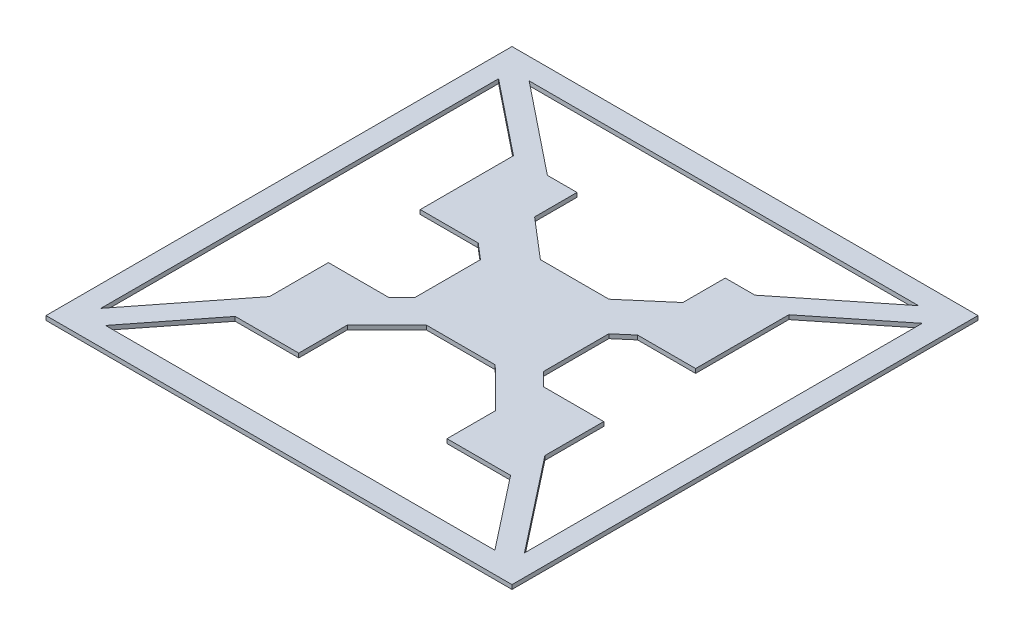
SolidWorks part; units mm, degrees
ref_plane "Спереди" through (0, 0, 0) normal (0, 0, 1) x (1, 0, 0)
ref_plane "Сверху" through (0, 0, 0) normal (0, 1, 0) x (1, 0, 0)
ref_plane "Справа" through (0, 0, 0) normal (1, 0, 0) x (0, 0, -1)
sketch "Эскиз1" plane through (0, 0, 0) normal (0, 1, 0) x (1, 0, 0)
  line L0 (0, 96.4569) -> (0, -119.3284) construction
  line L1 (-128.9937, 0) -> (115.7561, 0) construction
  line L2 (-48.9866, 65.6813) -> (-35, 65.6813)
  line L3 (-65, -21.6813) -> (-36.6417, -21.6813)
  line L4 (-65, -49.475) -> (-65, -21.6813)
  line L5 (-35, -65.6813) -> (-65, -65.6813)
  line L6 (35, -42.7008) -> (35, -65.6813)
  line L7 (36.6417, -21.6813) -> (65, -21.6813)
  line L8 (65, -49.475) -> (65, -21.6813)
  line L9 (-35, -65.6813) -> (-35, -42.7008)
  line L10 (-65, 21.6813) -> (-37.6274, 21.6813)
  line L11 (-16.1862, -24.1069) -> (16.1862, -24.1069)
  line L12 (-35, 45.6702) -> (-35, 65.6813)
  line L13 (-65, 65.6813) -> (-65, 21.6813)
  line L14 (100, 93.6652) -> (100, -94.1115)
  line L15 (35, 65.6813) -> (35, 45.6702)
  line L16 (37.6274, 21.6813) -> (65, 21.6813)
  line L17 (-91.9096, 100) -> (91.9096, 100)
  line L18 (-30.2984, 15.4121) -> (-30.2984, -15.4121)
  line L19 (-16.1862, 29.577) -> (16.1862, 29.577)
  line L20 (30.2984, -15.4121) -> (30.2984, 15.4121)
  line L21 (35, 59.4235) -> (65, 59.4235) construction
  line L22 (48.9866, 65.6813) -> (91.9096, 100)
  line L23 (-110, 110) -> (110, 110)
  line L24 (-110, 110) -> (-110, -110)
  line L25 (-110, -110) -> (110, -110)
  line L26 (110, 110) -> (110, -110)
  line L27 (-100, 93.6652) -> (-100, -94.1115)
  line L28 (35, -65.6813) -> (65, -65.6813)
  line L29 (-91.9096, -100) -> (91.9096, -100)
  line L30 (-65, 59.4235) -> (-35, 59.4235) construction
  line L31 (65, 65.6813) -> (100, 93.6652)
  line L32 (16.1862, 29.577) -> (35, 45.6702)
  line L33 (30.2984, 15.4121) -> (37.6274, 21.6813)
  line L34 (-91.9096, 100) -> (-48.9866, 65.6813)
  line L35 (-100, 93.6652) -> (-65, 65.6813)
  line L36 (-35, 45.6702) -> (-16.1862, 29.577)
  line L37 (-30.2984, 15.4121) -> (-37.6274, 21.6813)
  line L38 (30.2984, -15.4121) -> (36.6417, -21.6813)
  line L39 (16.1862, -24.1069) -> (35, -42.7008)
  line L40 (65, -49.475) -> (100, -94.1115)
  line L41 (65, -65.6813) -> (91.9096, -100)
  line L42 (-36.6417, -21.6813) -> (-30.2984, -15.4121)
  line L43 (-16.1862, -24.1069) -> (-35, -42.7008)
  line L44 (-65, -49.475) -> (-100, -94.1115)
  line L45 (-65, -65.6813) -> (-91.9096, -100)
  line L46 (48.9866, 65.6813) -> (35, 65.6813)
  line L47 (65, 65.6813) -> (65, 21.6813)
  line L48 (-65, -49.4291) -> (-35, -49.4291) construction
  line L49 (35, -49.4291) -> (65, -49.4291) construction
  point P8 (65, -35.5781)
  point P12 (-50, 59.4235)
  point P17 (50, 59.4235)
  point P20 (-50, -49.4291)
  point P22 (50, -49.4291)
  point P24 (0, 0)
  point P25 (0, 0)
  point P29 (0, 0)
  point P35 (0, 29.577)
  point P59 (0, -24.1069)
  point P69 (-30.2984, 0)
  point P70 (30.2984, 0)
  dimension "D15" = 10
  dimension "D1" = 30
  dimension "D2" = 44
  dimension "D3" = 220
  dimension "D4" = 44
  dimension "D5" = 220
  dimension "D6" = 30
  dimension "D7" = 30
  dimension "D8" = 44
  dimension "D9" = 30
  dimension "D10" = 44
  dimension "D11" = 100
  dimension "D12" = 10
  dimension "D13" = 10
  dimension "D14" = 10
  dimension "D16" = 10
  dimension "D17" = 10
  dimension "D18" = 10
  dimension "D19" = 10
  dimension "D20" = 100
extrude "Бобышка-Вытянуть1" add sketch "Эскиз1" along normal blind 2
